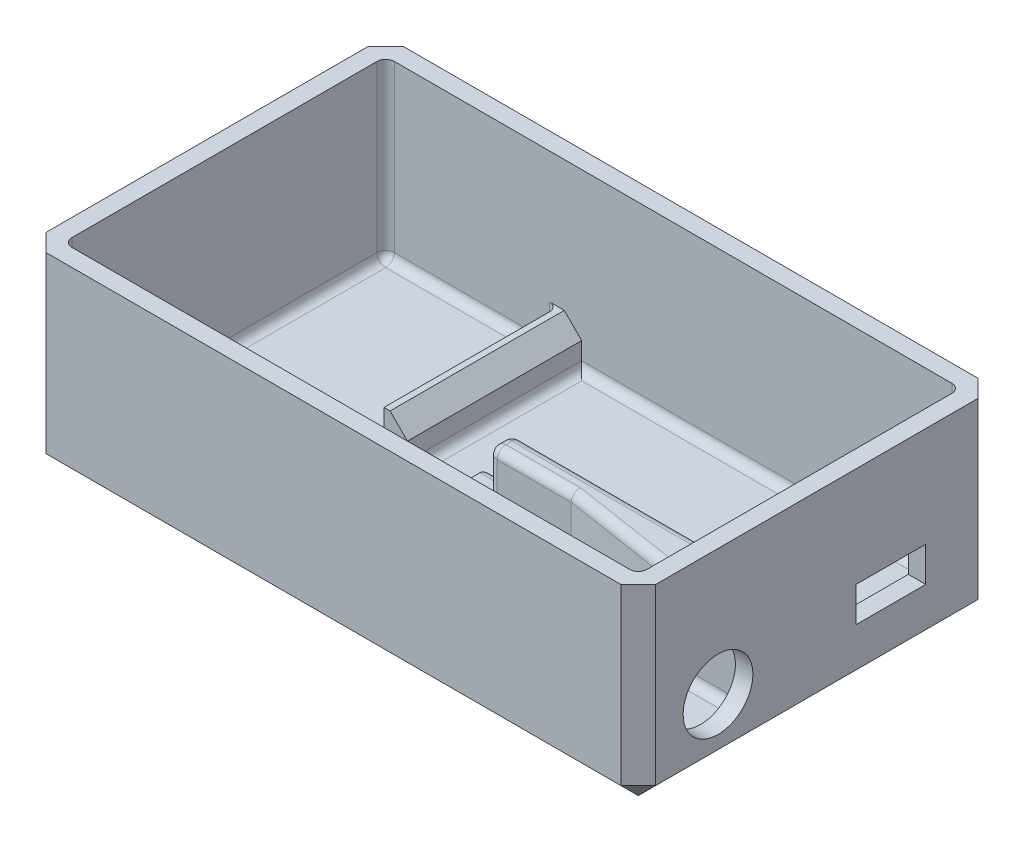
SolidWorks part; units mm, degrees
ref_plane "Plan de face" through (0, 0, 0) normal (0, 0, 1) x (1, 0, 0)
ref_plane "Plan de dessus" through (0, 0, 0) normal (0, 1, 0) x (1, 0, 0)
ref_plane "Plan de droite" through (0, 0, 0) normal (1, 0, 0) x (0, 0, -1)
sketch "Esquisse1" plane through (0, 0, 0) normal (0, 1, 0) x (1, 0, 0)
  line L1 (-35, 20.5) -> (35, 20.5)
  line L2 (-35, 20.5) -> (-35, -20.5)
  line L3 (-35, -20.5) -> (35, -20.5)
  line L4 (35, 20.5) -> (35, -20.5)
  line L5 (-35, 20.5) -> (35, -20.5) construction
  line L6 (-35, -20.5) -> (35, 20.5) construction
  point P0 (0, 0)
  dimension "D1" = 41
  dimension "D2" = 70
extrude "Boss.-Extru.1" add sketch "Esquisse1" along normal blind 22
shell "Coque1" thickness 2 removed face at (0, 22, 0)
sketch "Esquisse2" plane through (0, 2, 0) normal (0, 1, 0) x (1, 0, 0)
  line L0 (33, -16.5) -> (24, -16.5)
  line L1 (33, -18.5) -> (33, 18.5) construction
  line L2 (24, -16.5) -> (11, -18.5)
  line L3 (-33, -18.5) -> (33, -18.5) construction
  line L4 (11, -18.5) -> (33, -18.5)
  line L5 (33, -18.5) -> (33, -16.5)
  line L6 (33, -6.2) -> (24, -6.2)
  line L7 (24, -6.2) -> (11, -4.2)
  line L9 (33, -1.5) -> (33, -6.2)
  line L10 (11, -4.2) -> (1.5, -4.2)
  line L14 (1.5, -1.5) -> (33, -1.5)
  line L15 (1.5, -4.2) -> (1.5, -1.5)
  dimension "D1" = 14.3
  dimension "D2" = 10.3
  dimension "D3" = 2
  dimension "D4" = 4.7
  dimension "D5" = 9
  dimension "D6" = 9.5
  dimension "D7" = 31.5
extrude "Boss.-Extru.2" add sketch "Esquisse2" along normal blind 10
sketch "Esquisse3" plane through (33, 0, 0) normal (-1, 0, 0) x (0, 0, 1)
  line L0 (16.5, 2) -> (6.2, 2) construction
  line L1 (1.5, 2) -> (-18.5, 2) construction
  line L2 (-12.5, 6.5) -> (-4.5, 6.5)
  line L3 (-12.5, 6.5) -> (-12.5, 10.5)
  line L4 (-12.5, 10.5) -> (-4.5, 10.5)
  line L5 (-4.5, 6.5) -> (-4.5, 10.5)
  circle A0 centre (11.35, 7.5) radius 4
  point P4 (11.35, 2)
  point P11 (-8.5, 6.5)
  point P12 (-8.5, 2)
  dimension "D1" = 8
  dimension "D2" = 5.5
  dimension "D3" = 4.5
  dimension "D4" = 8
  dimension "D5" = 4
extrude "Enlèv. mat.-Extru.1" cut sketch "Esquisse3" against normal up to next
sketch "Esquisse4" plane through (-33, 0, 0) normal (1, 0, 0) x (0, 0, -1)
  circle A0 centre (-11.35, 7.5) radius 3.5
  circle A1 centre (-11.35, 7.5) radius 4 construction
  dimension "D1" = 7
extrude "Enlèv. mat.-Extru.2" cut sketch "Esquisse4" against normal up to next
sketch "Esquisse5" plane through (0, 2, 0) normal (0, 1, 0) x (1, 0, 0)
  line L0 (33, 18.5) -> (-33, 18.5) construction
  line L1 (-13.2, 18.5) -> (-10.5, 18.5)
  line L2 (-13.2, 18.5) -> (-13.2, -1.5)
  line L3 (-13.2, -1.5) -> (-10.5, -1.5)
  line L4 (-10.5, 18.5) -> (-10.5, -1.5)
  line L5 (-33, -18.5) -> (11, -18.5) construction
  line L6 (1.5, -1.5) -> (-1.2, -1.5)
  line L7 (1.5, -1.5) -> (1.5, -5.8)
  line L8 (1.5, -5.8) -> (-1.2, -5.8)
  line L9 (-1.2, -1.5) -> (-1.2, -5.8)
  line L10 (1.5, -18.5) -> (-1.2, -18.5)
  line L11 (1.5, -18.5) -> (1.5, -16.9)
  line L12 (1.5, -16.9) -> (-1.2, -16.9)
  line L13 (-1.2, -18.5) -> (-1.2, -16.9)
  line L14 (33, -1.5) -> (33, 18.5) construction
  line L16 (1.5, -4.2) -> (11, -4.2) construction
  line L17 (33, -1.5) -> (1.5, -1.5) construction
  dimension "D1" = 43.5
  dimension "D2" = 2.7
  dimension "D3" = 1.6
  dimension "D4" = 1.6
extrude "Boss.-Extru.3" add sketch "Esquisse5" along normal blind 5
fillet "Congé1" radius 1 43 edges at (28.5, 12, 6.2) (17.5, 12, 5.2) (6.25, 12, 4.2) (17.25, 12, 1.5) (1.5, 9.5, 4.2) (1.5, 9.5, 1.5) (22, 12, 18.5) (33, 12, 17.5) (33, 12, 3.85) (33, 7, 1.5) (28.5, 2, 16.5) (33, 7, 16.5) (33, 7, 6.2) (33, 17, 18.5) (33, 12, -18.5) (33, 2, 11.35) (17.5, 2, 17.5) (28.5, 2, 6.2) (17.5, 2, 5.2) (6.25, 2, 4.2) (15.9, 2, 1.5) (33, 2, -8.5) (6.25, 2, 18.5) (-17.1, 2, 18.5) (-33, 12, 18.5) (-33, 2, 0) (-23.1, 2, -18.5) (11.25, 2, -18.5) (-33, 12, -18.5) (1.5, 12, 2.85) (-1.2, 2, 17.7) (1.5, 2, 17.7) (0.15, 2, 16.9) (1.5, 2, 5) (0.15, 2, 5.8) (-1.2, 2, 3.65) (-11.85, 2, 1.5) (-10.5, 2, -8.5) (-13.2, 2, -8.5) (0.15, 7, 1.5) (-13.2, 4.5, -18.5) (-1.2, 4.5, 18.5) (-1.2, 4.5, 1.5)
chamfer "Chanfrein1" distance 2 angle 45 11 edges at (0, 0, -20.5) (35, 11, -20.5) (35, 0, 0) (35, 11, 20.5) (0, 0, 20.5) (-35, 11, 20.5) (-35, 0, 0) (-35, 11, -20.5) (1.5, 7, 17.7) (1.5, 7, 5) (-10.5, 7, -8.5)
